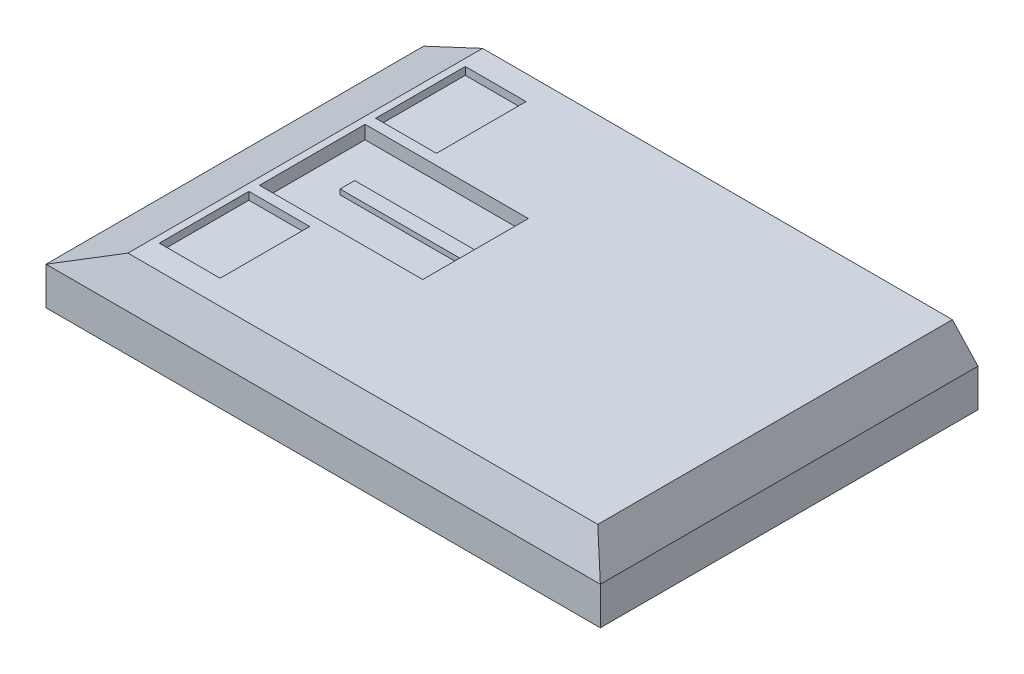
SolidWorks part; units mm, degrees
ref_plane "Front Plane" through (0, 0, 0) normal (0, 0, 1) x (1, 0, 0)
ref_plane "Top Plane" through (0, 0, 0) normal (0, 1, 0) x (1, 0, 0)
ref_plane "Right Plane" through (0, 0, 0) normal (1, 0, 0) x (0, 0, -1)
sketch "Sketch1" plane through (0, 0, 0) normal (0, 1, 0) x (1, 0, 0)
  line L1 (-219.964, -149.86) -> (0, -149.86)
  line L2 (-219.964, -149.86) -> (-219.964, 0)
  line L3 (-219.964, 0) -> (0, 0)
  line L4 (0, -149.86) -> (0, 0)
  dimension "D1" = 149.86
  dimension "D2" = 219.964
ref_plane "MiddleTop" through (0, 14.986, 0) normal (0, 1, 0) x (1, 0, 0)
sketch "Sketch2" plane through (0, 14.986, 0) normal (0, 1, 0) x (1, 0, 0)
  line L1 (0, 0) -> (-219.964, 0)
  line L2 (0, 0) -> (0, -149.86)
  line L3 (0, -149.86) -> (-219.964, -149.86)
  line L4 (-219.964, 0) -> (-219.964, -149.86)
extrude "Boss-Extrude1" add sketch "Sketch1" along normal blind 14.986
ref_plane "Plane2" through (0, 30.48, 0) normal (0, 1, 0) x (1, 0, 0)
sketch "Sketch3" plane through (0, 30.48, 0) normal (0, 1, 0) x (1, 0, 0)
  line L0 (0, -149.86) -> (-219.964, -149.86) construction
  line L1 (-192.024, -4.572) -> (-5.588, -4.572)
  line L2 (-192.024, -4.572) -> (-192.024, -145.288)
  line L3 (-192.024, -145.288) -> (-5.588, -145.288)
  line L4 (-5.588, -4.572) -> (-5.588, -145.288)
  line L5 (-219.964, 0) -> (-219.964, -149.86) construction
  line L6 (0, 0) -> (0, -149.86) construction
  dimension "D1" = 140.716
  dimension "D2" = 4.572
  dimension "D3" = 27.94
  dimension "D4" = 5.588
loft "Loft1" add profiles "Sketch2", "Sketch3" connector at (-219.964, 14.986, 149.86) connector at (-192.024, 30.48, 145.288)
sketch "Sketch4" plane through (0, 30.48, 0) normal (0, 1, 0) x (1, 0, 0)
  line L0 (-192.024, -145.288) -> (-5.588, -145.288) construction
  line L1 (-189.23, -135.636) -> (-165.1, -135.636)
  line L2 (-189.23, -135.636) -> (-189.23, -100.076)
  line L3 (-189.23, -100.076) -> (-165.1, -100.076)
  line L4 (-165.1, -135.636) -> (-165.1, -100.076)
  line L5 (-192.024, -4.572) -> (-192.024, -145.288) construction
  line L6 (-5.588, -4.572) -> (-192.024, -4.572) construction
  line L7 (-189.23, -49.784) -> (-165.1, -49.784)
  line L8 (-189.23, -49.784) -> (-189.23, -14.224)
  line L9 (-189.23, -14.224) -> (-165.1, -14.224)
  line L10 (-165.1, -49.784) -> (-165.1, -14.224)
  point P12 (-177.165, -14.224)
  dimension "D1" = 35.56
  dimension "D2" = 24.13
  dimension "D3" = 9.652
  dimension "D4" = 2.794
  dimension "D5" = 24.13
  dimension "D6" = 35.56
  dimension "D7" = 2.794
  dimension "D8" = 9.652
sketch "Sketch5" plane through (0, 30.48, 0) normal (0, 1, 0) x (1, 0, 0)
  line L0 (-189.23, -100.076) -> (-165.1, -100.076) construction
  line L1 (-189.23, -95.885) -> (-124.46, -95.885)
  line L2 (-189.23, -95.885) -> (-189.23, -53.975)
  line L3 (-189.23, -53.975) -> (-124.46, -53.975)
  line L4 (-124.46, -95.885) -> (-124.46, -53.975)
  line L5 (-192.024, -4.572) -> (-192.024, -145.288) construction
  dimension "D1" = 41.91
  dimension "D2" = 4.191
  dimension "D3" = 2.794
  dimension "D4" = 64.77
extrude "Cut-Extrude1" cut sketch "Sketch4" against normal blind 3.048
extrude "Cut-Extrude2" cut sketch "Sketch5" against normal blind 5.334
ref_plane "Plane3" through (0, 25.146, 0) normal (0, 1, 0) x (1, 0, 0)
sketch "Sketch6" plane through (0, 25.146, 0) normal (0, 1, 0) x (1, 0, 0)
  line L0 (-189.23, -53.975) -> (-189.23, -95.885) construction
  line L1 (-175.26, -72.0598) -> (-124.46, -72.0598)
  line L2 (-175.26, -72.0598) -> (-175.26, -77.851)
  line L3 (-175.26, -77.851) -> (-124.46, -77.851)
  line L4 (-124.46, -72.0598) -> (-124.46, -77.851)
  line L5 (-189.23, -95.885) -> (-124.46, -95.885) construction
  dimension "D1" = 50.8
  dimension "D2" = 13.97
  dimension "D3" = 5.7912
  dimension "D4" = 18.034
extrude "Boss-Extrude2" add sketch "Sketch6" along normal blind 2.032
sketch "Sketch10" plane through (0, 30.48, 0) normal (0, 1, 0) x (1, 0, 0)
  line L5 (-101.7258, -149.86) -> (-101.7258, -146.4838)
  line L6 (-219.964, -149.86) -> (0, -149.86) construction
  line L7 (-101.7258, -146.4838) -> (-98.7235, -146.4838)
  line L8 (-98.7235, -146.4838) -> (-98.7235, -143.4815)
  line L9 (-98.7235, -143.4815) -> (-103.6022, -143.4815)
  line L10 (-103.6022, -143.4815) -> (-103.6022, -134.3496)
  line L11 (-103.6022, -134.3496) -> (-101.1629, -134.3496)
  line L12 (-101.1629, -134.3496) -> (-101.1629, -130.2215)
  line L13 (-101.1629, -130.2215) -> (-21.1653, -130.2215)
  line L14 (-21.1653, -130.2215) -> (-21.1653, -133.0987)
  line L15 (-21.1653, -133.0987) -> (-16.1615, -133.0987)
  line L16 (-16.1615, -133.0987) -> (-16.1615, -143.4815)
  line L17 (-16.1615, -143.4815) -> (-22.6664, -143.4815)
  line L18 (-22.6664, -143.4815) -> (-22.6664, -146.4838)
  line L19 (-22.6664, -146.4838) -> (-17.6626, -146.4838)
  line L20 (-17.6626, -146.4838) -> (-17.6626, -149.86)
  line L21 (-17.6626, -149.86) -> (-101.7258, -149.86)
